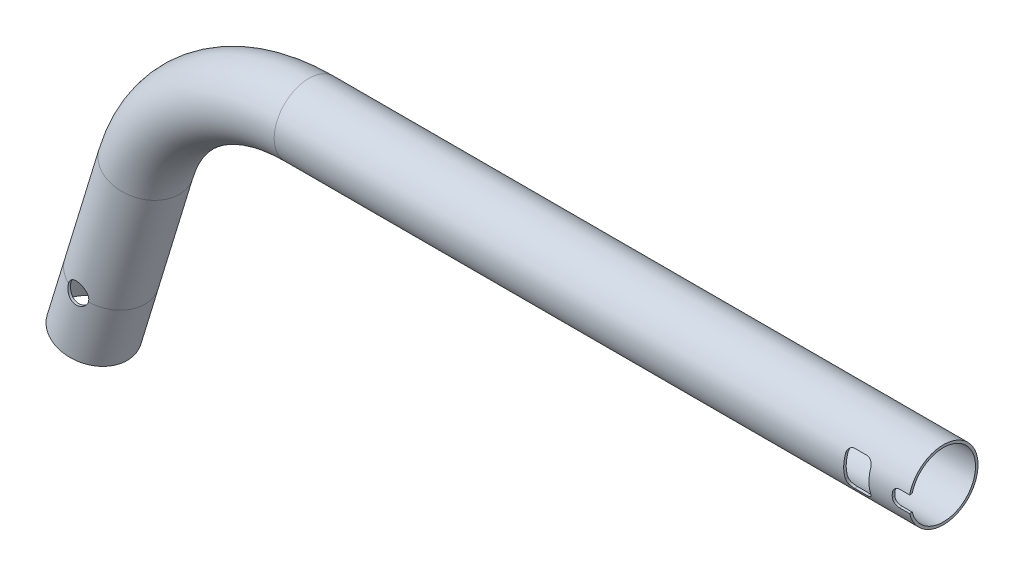
SolidWorks part; units mm, degrees
ref_plane "Front Plane" through (0, 0, 0) normal (0, 0, 1) x (1, 0, 0)
ref_plane "Top Plane" through (0, 0, 0) normal (0, 1, 0) x (1, 0, 0)
ref_plane "Right Plane" through (0, 0, 0) normal (1, 0, 0) x (0, 0, -1)
sketch "Sketch1" plane through (0, 0, 0) normal (0, 0, 1) x (1, 0, 0)
  line L0 (-92.2396, 0) -> (92.2396, 0)
  line L1 (-143.88, -38.2119) -> (-154.7604, -73.8)
  line L2 (92.2396, 0) -> (108.8396, 0)
  line L3 (-154.7604, -73.8) -> (-160.3247, -92)
  arc A0 (-92.2396, 0) -> (-143.88, -38.2119) centre (-92.2396, -54) ccw
  point P4 (0, 0)
  point P10 (-154.7604, -73.8)
  dimension "D2" = 54
  dimension "D1" = 73
  dimension "D3" = 73.8
  dimension "D4" = 247
  dimension "D5" = 92
  dimension "D6" = 73
  dimension "D7" = 16.6
ref_plane "Plane1" through (92.2396, 0, 0) normal (1, 0, 0) x (0, 0, -1)
sketch "Sketch3" plane through (92.2396, 0, 0) normal (1, 0, 0) x (0, 0, -1)
  circle A0 centre (0, 0) radius 11
  circle A1 centre (0, 0) radius 10.2
  dimension "D1" = 0.8
sweep "Sweep2" add profiles "Sketch3" path "Sketch1"
ref_axis "Axis1" through (108.8396, 0, 0) along (-1, 0, 0)
ref_axis "Axis2" through (-142.0816, -32.3296, 0) along (-0.2924, -0.9563, 0)
sketch "Sketch4" plane through (0, 0, 0) normal (0, 0, 1) x (1, 0, 0)
  line L0 (-165.2798, -70.5839) -> (-144.2411, -77.0161) construction
  line L1 (92.2396, -101.4635) -> (92.2396, 101.4635) construction
  line L2 (108.8396, 0) -> (92.2396, 0) construction
  line L3 (108.8396, -11) -> (108.8396, 11) construction
  line L4 (108.8396, 0) -> (-92.2396, 0) construction
  line L5 (108.8396, 2.5555) -> (108.8396, -2.5555)
  line L6 (90.2396, -5.5) -> (94.2396, -5.5)
  line L7 (88.2396, -3.5) -> (88.2396, 3.5)
  line L8 (90.2396, 5.5) -> (94.2396, 5.5)
  line L9 (96.2396, -3.5) -> (96.2396, 3.5)
  line L10 (88.2396, -5.5) -> (96.2396, 5.5) construction
  line L11 (88.2396, 5.5) -> (96.2396, -5.5) construction
  line L12 (105.6396, -2.5555) -> (108.8396, -2.5555)
  line L13 (103.6396, -0.5555) -> (103.6396, 0.5555)
  line L14 (105.6396, 2.5555) -> (108.8396, 2.5555)
  line L16 (103.6396, -2.5555) -> (108.8396, 0) construction
  line L17 (103.6396, 2.5555) -> (108.8396, 0) construction
  circle A0 centre (-154.7604, -73.8) radius 3.3
  arc A1 (90.2396, -5.5) -> (88.2396, -3.5) centre (90.2396, -3.5) cw
  arc A2 (96.2396, -3.5) -> (94.2396, -5.5) centre (94.2396, -3.5) cw
  arc A3 (94.2396, 5.5) -> (96.2396, 3.5) centre (94.2396, 3.5) cw
  arc A4 (90.2396, 5.5) -> (88.2396, 3.5) centre (90.2396, 3.5) ccw
  arc A5 (105.6396, -2.5555) -> (103.6396, -0.5555) centre (105.6396, -0.5555) cw
  arc A6 (103.6396, 0.5555) -> (105.6396, 2.5555) centre (105.6396, 0.5555) cw
  dimension "D1" = 16.6
  dimension "D4" = 2
  dimension "D5" = 2
  dimension "D2" = 8
  dimension "D3" = 11
extrude "Cut-Extrude1" cut sketch "Sketch4" along normal up to next
sketch "Sketch5" plane through (0, 0, 0) normal (0, 0, 1) x (1, 0, 0)
  line L0 (-164.5147, -70.8178) -> (-145.0061, -76.7822) construction
  circle A0 centre (-154.7604, -73.8) radius 3.3
extrude "Cut-Extrude2" cut sketch "Sketch5" against normal through all
